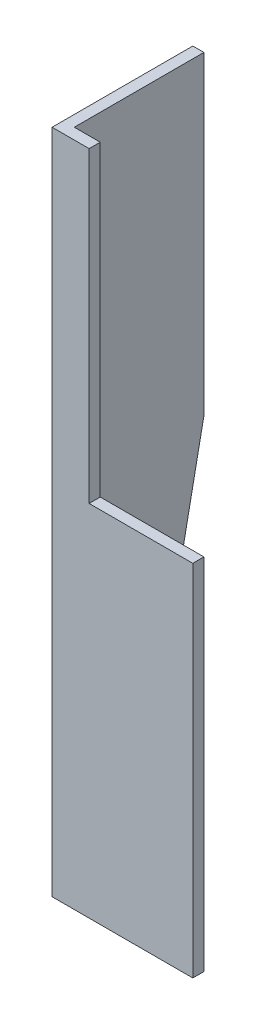
SolidWorks part; units mm, degrees
ref_plane "Alzado" through (0, 0, 0) normal (0, 0, 1) x (1, 0, 0)
ref_plane "Planta" through (0, 0, 0) normal (0, 1, 0) x (1, 0, 0)
ref_plane "Vista lateral" through (0, 0, 0) normal (1, 0, 0) x (0, 0, -1)
sketch "Croquis1" plane through (0, 0, 0) normal (0, 1, 0) x (1, 0, 0)
  line L0 (0, 0) -> (0, 38)
  line L1 (0, 0) -> (38, 0)
  line L2 (3, 3) -> (38, 3)
  line L3 (3, 3) -> (3, 38)
  line L4 (0, 38) -> (3, 38)
  line L5 (38, 3) -> (38, 0)
  dimension "D1" = 38
  dimension "D2" = 3
extrude "Saliente-Extruir1" add sketch "Croquis1" along normal blind 180
sketch "Croquis2" plane through (0, 0, 0) normal (-1, 0, 0) x (0, 0, 1)
  line L0 (-38, 95) -> (0, 95) construction
  line L1 (-38, 180) -> (-38, 0) construction
  line L2 (0, 180) -> (0, 0) construction
  line L3 (-38, 180) -> (0, 180) construction
  line L4 (-38, 95) -> (-19, 0)
  line L5 (-38, 0) -> (0, 0) construction
  line L6 (-19, 0) -> (0, 0)
  line L9 (-38, 95) -> (-38, 0)
  line L10 (-38, 0) -> (-19, 0)
  line M8 (-38, 0) -> (0, 0)
  line M11 (-38, 180) -> (-38, 0)
  dimension "D1" = 85
  dimension "D2" = 19
extrude "Cortar-Extruir1" cut sketch "Croquis2" against normal up to surface (3 mm away) contours L4 M11 M8 region at (0, 31.6667, -31.6667) up to face at (3, 90, -20.5)
sketch "Croquis3" plane through (0, 0, 0) normal (0, 0, 1) x (1, 0, 0)
  line L0 (0, 180) -> (0, 0) construction
  line L1 (38, 180) -> (10, 180)
  line L2 (38, 180) -> (38, 97)
  line L3 (38, 97) -> (10, 97)
  line L4 (10, 180) -> (10, 97)
  dimension "D1" = 10
  dimension "D2" = 83
extrude "Cortar-Extruir2" cut sketch "Croquis3" against normal up to surface (3 mm away) up to face at (20.5, 90, -3)
